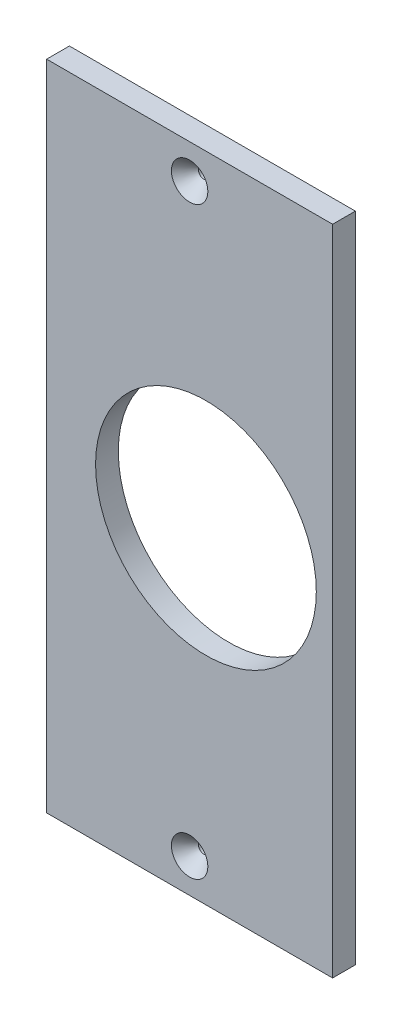
SolidWorks part; units mm, degrees
material "Beech"
ref_plane "Front Plane" through (0, 0, 0) normal (0, 0, 1) x (1, 0, 0)
ref_plane "Top Plane" through (0, 0, 0) normal (0, 1, 0) x (1, 0, 0)
ref_plane "Right Plane" through (0, 0, 0) normal (1, 0, 0) x (0, 0, -1)
sketch "Sketch1" plane through (0, 0, 0) normal (0, 0, 1) x (1, 0, 0)
  line L1 (-234.753, 19.05) -> (-314.5466, 19.05)
  line L2 (-234.753, 19.05) -> (-234.753, -163.1)
  line L3 (-234.753, -163.1) -> (-314.5466, -163.1)
  line L4 (-314.5466, 19.05) -> (-314.5466, -163.1)
  line L5 (-234.753, -163.1) -> (-350.6408, -163.1) construction
  dimension "D1" = 79.7937
extrude "Boss-Extrude1" add sketch "Sketch1" along normal blind 6.35 contours L4 L3 L2 L1
hole_wizard "1/4 (0.25) Diameter Hole1" positions "Sketch4" profile "Sketch5" hole size "1/4" standard "ANSI Inch" end condition through all
sketch "Sketch4" plane through (0, 0, 6.35) normal (0, 0, 1) x (1, 0, 0)
  point P0 (-270.0966, -72.025)
sketch "Sketch5" plane through (-270.0966, -72.025, 6.35) normal (1, 0, 0) x (0, -1, 0)
  line L0 (0, 0) -> (0, 6.35)
  line L1 (0, 6.35) -> (3.175, 6.35)
  line L2 (3.175, 6.35) -> (3.175, 0)
  line L5 (3.175, 0) -> (0, 0)
  line L11 (0, -6.35) -> (0, 107.95) construction
  dimension "Thru Hole Dia." = 6.35
  dimension "Thru Hole Depth" = 6.35
hole_wizard "Hole1" positions "Sketch6" profile "Sketch7" legacy
sketch "Sketch6" plane through (181.0394, -72.025, 6.35) normal (0, 0, 1) x (0, 1, 0)
  line L0 (91.075, 455.6892) -> (-91.075, 455.6892) construction
  point P0 (81.55, 455.6892)
  point P2 (-81.55, 455.6892)
sketch "Sketch7" plane through (-274.6498, 9.525, 6.35) normal (1, 0, 0) x (0, -1, 0)
  line L0 (0, 0) -> (0, 32.7039)
  line L1 (0, 32.7039) -> (1.5875, 31.75)
  line L2 (1.5875, 31.75) -> (1.5875, 4.0177)
  line L3 (1.5875, 4.0177) -> (5.08, 0)
  line L4 (5.08, 0) -> (0, 0)
  line L5 (0, -14.3089) -> (0, 102.4216) construction
  line L6 (0, 32.7039) -> (-1.5875, 31.75) construction
  line L7 (-1.5875, 4.0177) -> (-5.08, 0) construction
  dimension "Diameter" = 3.175
  dimension "Depth" = 31.75
  dimension "C-Sink Diameter" = 10.16
  dimension "C-Sink Angle" = 82
  dimension "Drill Angle" = 118
sketch "Sketch8" plane through (0, 0, 6.35) normal (0, 0, 1) x (1, 0, 0)
  circle A0 centre (-270.0966, -72.025) radius 30.7975
  dimension "D1" = 61.595
extrude "Cut-Extrude1" cut sketch "Sketch8" against normal through all
